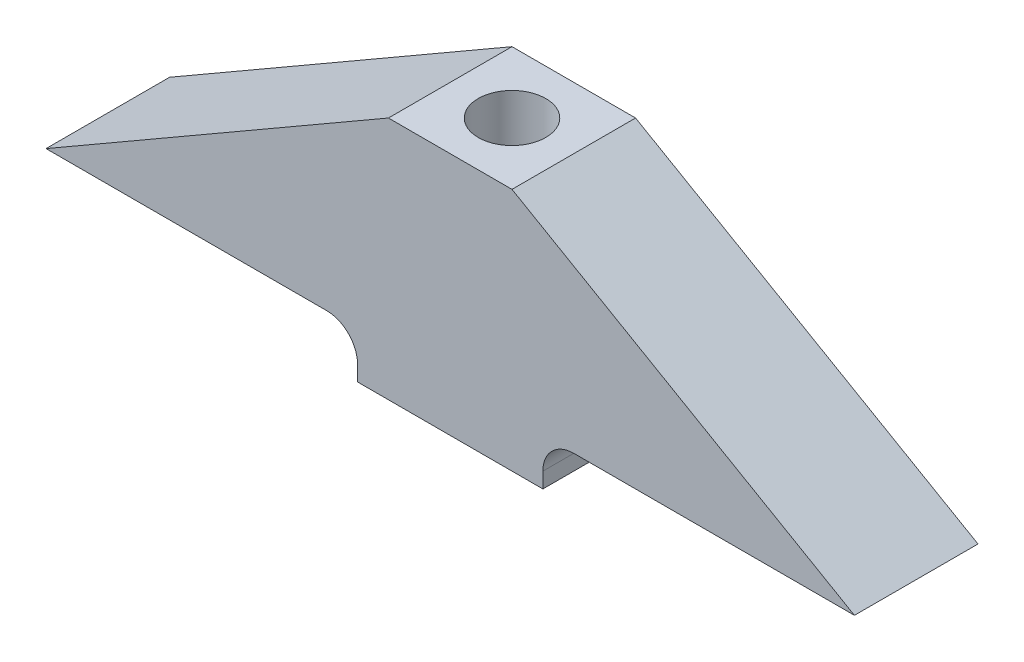
SolidWorks part; units mm, degrees
material "6061-T6 (SS)"
ref_plane "Front Plane" through (0, 0, 0) normal (0, 0, 1) x (1, 0, 0)
ref_plane "Top Plane" through (0, 0, 0) normal (0, 1, 0) x (1, 0, 0)
ref_plane "Right Plane" through (0, 0, 0) normal (1, 0, 0) x (0, 0, -1)
sketch "Sketch1" plane through (0, 0, 0) normal (0, 0, 1) x (1, 0, 0)
  line L0 (0, 0) -> (64.0405, 0)
  line L1 (166.1811, 0) -> (95.7905, 40.64)
  line L2 (95.7905, 40.64) -> (70.3905, 40.64)
  line L3 (70.3905, 40.64) -> (0, 0)
  line L4 (64.0405, 0) -> (64.0405, -9.525)
  line L5 (64.0405, -9.525) -> (102.1405, -9.525)
  line L6 (102.1405, -9.525) -> (102.1405, 0)
  line L7 (102.1405, 0) -> (166.1811, 0)
  point P8 (83.0905, -9.525)
  point P10 (83.0905, 40.64)
  dimension "D1" = 30
  dimension "D2" = 30
  dimension "D3" = 25.4
  dimension "D4" = 40.64
  dimension "D5" = 9.525
  dimension "D6" = 38.1
extrude "Boss-Extrude1" add sketch "Sketch1" along normal blind 25.4
hole_wizard "35/64 (0.54688) Diameter Hole1" positions "Sketch2" profile "Sketch3" hole size "35/64" standard "ANSI Inch"
sketch "Sketch2" plane through (0, 40.64, 0) normal (0, 1, 0) x (1, 0, 0)
  point P0 (83.0905, -12.7)
  dimension "D1" = 12.7
  dimension "D2" = 12.7
sketch "Sketch3" plane through (83.0905, 40.64, 12.7) normal (1, 0, 0) x (0, 0, 1)
  line L0 (0, 0) -> (0, 39.2252)
  line L1 (0, 39.2252) -> (6.9454, 35.052)
  line L2 (6.9454, 35.052) -> (6.9454, 0)
  line L5 (6.9454, 0) -> (0, 0)
  line L10 (0, 39.2252) -> (-6.9454, 35.052) construction
  line L11 (0, -6.35) -> (0, 107.95) construction
  dimension "Hole Dia." = 13.8908
  dimension "Hole Depth" = 35.052
  dimension "Drill Angle" = 118
hole_wizard "1/4-28 Tapped Hole1" positions "Sketch4" profile "Sketch5" tap size "1/4-28" standard "ANSI Inch"
sketch "Sketch4" plane through (0, -9.525, 0) normal (0, -1, 0) x (-1, 0, 0)
  point P0 (-92.6155, -15.875)
  point P3 (-73.5655, -9.525)
  point P11 (-64.0405, 0)
  point P16 (0, 0)
  dimension "D1" = 9.525
  dimension "D2" = 9.525
  dimension "D3" = 9.525
  dimension "D4" = 9.525
sketch "Sketch5" plane through (92.6155, -9.525, 15.875) normal (1, 0, 0) x (0, 0, -1)
  line L0 (0, 0) -> (0, 10.7694)
  line L1 (0, 10.7694) -> (2.7051, 9.144)
  line L2 (2.7051, 9.144) -> (2.7051, 0)
  line L5 (2.7051, 0) -> (0, 0)
  line L10 (0, 10.7694) -> (-2.7051, 9.144) construction
  line L11 (0, -6.35) -> (0, 107.95) construction
  dimension "Tap Drill Dia." = 5.4102
  dimension "Tap Drill Depth" = 9.144
  dimension "Drill Angle" = 118
cosmetic thread "Hole Thread1" parameters "D1"=6.35, "D2"=6.35
cosmetic thread "Hole Thread2" parameters "D1"=6.35, "D2"=6.35
fillet "Fillet1" radius 6.35 2 edges at (102.1405, 0, 12.7) (64.0405, 0, 12.7)
